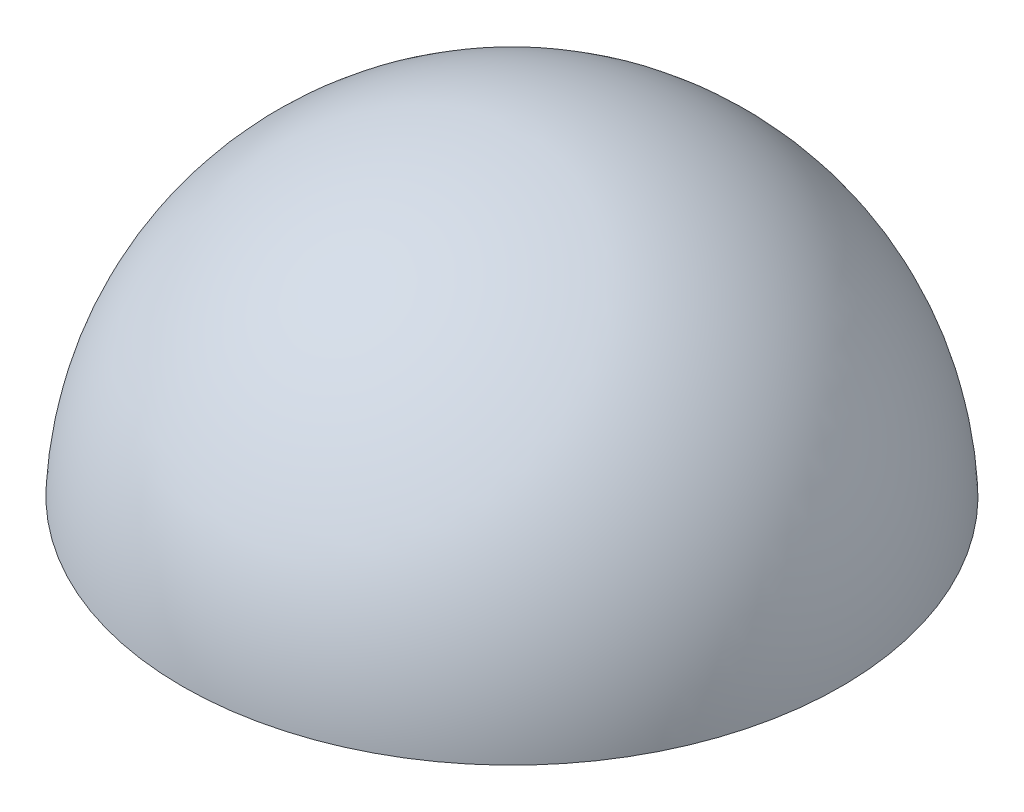
SolidWorks part; units mm, degrees
ref_plane "Front Plane" through (0, 0, 0) normal (0, 0, 1) x (1, 0, 0)
ref_plane "Top Plane" through (0, 0, 0) normal (0, 1, 0) x (1, 0, 0)
ref_plane "Right Plane" through (0, 0, 0) normal (1, 0, 0) x (0, 0, -1)
sketch "Sketch1" plane through (0, 0, 0) normal (0, 1, 0) x (1, 0, 0)
  line L0 (0, -44.45) -> (0, 44.45)
  arc A0 (0, 44.45) -> (0, -44.45) centre (0, 0) ccw
  arc A1 (0, 42.45) -> (0, -42.45) centre (0, 0) ccw
  circle A3 centre (0, 0) radius 44.45 construction
  circle A4 centre (0, 0) radius 42.45 construction
  point P1 (42.45, 0)
  point P6 (42.5077, 12.9959)
  dimension "D1" = 88.9
  dimension "D2" = 2
revolve "Revolve1" add sketch "Sketch1" angle 180 about L0 region at (-43.4561, 0, 0)
sketch "Sketch2" plane through (0, 0, 0) normal (0, 1, 0) x (1, 0, 0)
  circle A0 centre (0, 0) radius 44.45
extrude "Cut-Extrude1" cut sketch "Sketch2" along normal blind 2
sketch "30deg" plane through (0, 0, 0) normal (1, 0, 0) x (0, 0, -1)
  line L0 (0, 0) -> (38.4948, 22.225) construction
  line L1 (0, 0) -> (44.45, 0) construction
  line L7 (0, 0) -> (22.225, 38.4948) construction
  line L8 (0, 0) -> (44.45, 0) construction
  line L10 (0, 0) -> (38.4948, 22.225) construction
  line L25 (0, 0) -> (0, 49000) construction
  dimension "D2" = 3
  dimension "D3" = 30
  dimension "D1" = 44.45
sketch "Sketch4" plane through (0, 0, 0) normal (0, 1, 0) x (1, 0, 0)
  line L0 (0, 0) -> (0, 43.45)
  line L1 (0.5, 44.45) -> (-0.5, 44.45)
  line L2 (-0.5, 43.45) -> (0.5, 43.45)
  line L3 (-0.5, 43.45) -> (-0.5, 44.45)
  line L4 (0.5, 43.45) -> (0.5, 44.45)
  line L5 (0, 0) -> (21.725, 37.6288)
  line L6 (21.292, 37.8788) -> (21.792, 38.7448)
  line L7 (21.292, 37.8788) -> (22.158, 37.3788)
  line L8 (22.158, 37.3788) -> (22.658, 38.2448)
  line L9 (22.658, 38.2448) -> (21.792, 38.7448)
  line L10 (0, 0) -> (37.6288, 21.725)
  line L11 (37.3788, 22.158) -> (38.2448, 22.658)
  line L12 (37.3788, 22.158) -> (37.8788, 21.292)
  line L13 (37.8788, 21.292) -> (38.7448, 21.792)
  line L14 (38.7448, 21.792) -> (38.2448, 22.658)
  line L15 (0, 0) -> (43.45, 0)
  line L16 (43.45, 0.5) -> (44.45, 0.5)
  line L17 (43.45, 0.5) -> (43.45, -0.5)
  line L18 (43.45, -0.5) -> (44.45, -0.5)
  line L19 (44.45, -0.5) -> (44.45, 0.5)
  line L20 (0, 0) -> (37.6288, -21.725)
  line L21 (37.8788, -21.292) -> (38.7448, -21.792)
  line L22 (37.8788, -21.292) -> (37.3788, -22.158)
  line L23 (37.3788, -22.158) -> (38.2448, -22.658)
  line L24 (38.2448, -22.658) -> (38.7448, -21.792)
  line L25 (0, 0) -> (21.725, -37.6288)
  line L26 (22.158, -37.3788) -> (22.658, -38.2448)
  line L27 (22.158, -37.3788) -> (21.292, -37.8788)
  line L28 (21.292, -37.8788) -> (21.792, -38.7448)
  line L29 (21.792, -38.7448) -> (22.658, -38.2448)
  line L30 (0, 0) -> (0, -43.45)
  line L31 (0.5, -43.45) -> (0.5, -44.45)
  line L32 (0.5, -43.45) -> (-0.5, -43.45)
  line L33 (-0.5, -43.45) -> (-0.5, -44.45)
  line L34 (-0.5, -44.45) -> (0.5, -44.45)
  line L35 (0, 0) -> (-21.725, -37.6288)
  line L36 (-21.292, -37.8788) -> (-21.792, -38.7448)
  line L37 (-21.292, -37.8788) -> (-22.158, -37.3788)
  line L38 (-22.158, -37.3788) -> (-22.658, -38.2448)
  line L39 (-22.658, -38.2448) -> (-21.792, -38.7448)
  line L40 (0, 0) -> (-37.6288, -21.725)
  line L41 (-37.3788, -22.158) -> (-38.2448, -22.658)
  line L42 (-37.3788, -22.158) -> (-37.8788, -21.292)
  line L43 (-37.8788, -21.292) -> (-38.7448, -21.792)
  line L44 (-38.7448, -21.792) -> (-38.2448, -22.658)
  line L45 (0, 0) -> (-43.45, 0)
  line L46 (-43.45, -0.5) -> (-44.45, -0.5)
  line L47 (-43.45, -0.5) -> (-43.45, 0.5)
  line L48 (-43.45, 0.5) -> (-44.45, 0.5)
  line L49 (-44.45, 0.5) -> (-44.45, -0.5)
  line L50 (0, 0) -> (-37.6288, 21.725)
  line L51 (-37.8788, 21.292) -> (-38.7448, 21.792)
  line L52 (-37.8788, 21.292) -> (-37.3788, 22.158)
  line L53 (-37.3788, 22.158) -> (-38.2448, 22.658)
  line L54 (-38.2448, 22.658) -> (-38.7448, 21.792)
  line L55 (0, 0) -> (-21.725, 37.6288)
  line L56 (-22.158, 37.3788) -> (-22.658, 38.2448)
  line L57 (-22.158, 37.3788) -> (-21.292, 37.8788)
  line L58 (-21.292, 37.8788) -> (-21.792, 38.7448)
  line L59 (-21.792, 38.7448) -> (-22.658, 38.2448)
  line L60 (0, 0) -> (0, 43.45) construction
  line L61 (0, 0) -> (21.725, 37.6288) construction
  circle A0 centre (0, 0) radius 44.45 construction
  point P7 (0, 44.45)
  point P10 (0, 43.45)
  dimension "D1" = 88.9
  dimension "D2" = 1
  dimension "D3" = 1
  dimension "D5" = 30
  dimension "D4" = 12
ref_plane "Plane1" through (0, 44.45, 0) normal (0, 1, 0) x (1, 0, 0)
sketch "Sketch5" plane through (0, 44.45, 0) normal (0, 1, 0) x (1, 0, 0)
  circle A0 centre (0, 0) radius 0.5
  dimension "D1" = 1
sketch "Sketch6" plane through (0, 0, 0) normal (0, 0, 1) x (1, 0, 0)
  line L0 (44.45, 0) -> (-44.45, 0) construction
  line L1 (-43.45, 0) -> (-44.45, 0) construction
  arc A0 (-44.45, 0) -> (0, 44.45) centre (0, 0) cw
ref_axis "Axis1" through (0, 117.8347, 0) along (0, -1, 0)
sketch "Sketch7" plane through (0, 44.45, 0) normal (0, 1, 0) x (1, 0, 0)
  line L0 (0, 0) -> (0, 88.8986) construction
  line L4 (-0.5, 38.9916) -> (-0.5, 88.8986)
  line L5 (0.5, 38.9916) -> (0.5, 88.8986)
  line L7 (-0.5, 22.7195) -> (-0.5, 37.9915)
  line L9 (0.5, 22.7195) -> (0.5, 37.9915)
  line L10 (0, 0) -> (44.4493, 76.9884) construction
  line L11 (19.0628, 34.0177) -> (44.0163, 77.2384)
  line L12 (19.9288, 33.5177) -> (44.8823, 76.7384)
  line L13 (10.9267, 19.9257) -> (18.5628, 33.1516)
  line L14 (11.7928, 19.4257) -> (19.4288, 32.6516)
  line L17 (0, 0) -> (76.9884, 44.4493) construction
  line L18 (33.5177, 19.9288) -> (76.7384, 44.8823)
  line L19 (34.0177, 19.0628) -> (77.2384, 44.0163)
  line L20 (19.4257, 11.7928) -> (32.6516, 19.4288)
  line L21 (19.9257, 10.9267) -> (33.1516, 18.5628)
  line L24 (0, 0) -> (88.8986, 0) construction
  line L25 (38.9916, 0.5) -> (88.8986, 0.5)
  line L26 (38.9916, -0.5) -> (88.8986, -0.5)
  line L27 (22.7195, 0.5) -> (37.9915, 0.5)
  line L28 (22.7195, -0.5) -> (37.9915, -0.5)
  line L31 (0, 0) -> (76.9884, -44.4493) construction
  line L32 (34.0177, -19.0628) -> (77.2384, -44.0163)
  line L33 (33.5177, -19.9288) -> (76.7384, -44.8823)
  line L34 (19.9257, -10.9267) -> (33.1516, -18.5628)
  line L35 (19.4257, -11.7928) -> (32.6516, -19.4288)
  line L38 (0, 0) -> (44.4493, -76.9884) construction
  line L39 (19.9288, -33.5177) -> (44.8823, -76.7384)
  line L40 (19.0628, -34.0177) -> (44.0163, -77.2384)
  line L41 (11.7928, -19.4257) -> (19.4288, -32.6516)
  line L42 (10.9267, -19.9257) -> (18.5628, -33.1516)
  line L45 (0, 0) -> (0, -88.8986) construction
  line L46 (0.5, -38.9916) -> (0.5, -88.8986)
  line L47 (-0.5, -38.9916) -> (-0.5, -88.8986)
  line L48 (0.5, -22.7195) -> (0.5, -37.9915)
  line L49 (-0.5, -22.7195) -> (-0.5, -37.9915)
  line L52 (0, 0) -> (-44.4493, -76.9884) construction
  line L53 (-19.0628, -34.0177) -> (-44.0163, -77.2384)
  line L54 (-19.9288, -33.5177) -> (-44.8823, -76.7384)
  line L55 (-10.9267, -19.9257) -> (-18.5628, -33.1516)
  line L56 (-11.7928, -19.4257) -> (-19.4288, -32.6516)
  line L59 (0, 0) -> (-76.9884, -44.4493) construction
  line L60 (-33.5177, -19.9288) -> (-76.7384, -44.8823)
  line L61 (-34.0177, -19.0628) -> (-77.2384, -44.0163)
  line L62 (-19.4257, -11.7928) -> (-32.6516, -19.4288)
  line L63 (-19.9257, -10.9267) -> (-33.1516, -18.5628)
  line L66 (0, 0) -> (-88.8986, 0) construction
  line L67 (-38.9916, -0.5) -> (-88.8986, -0.5)
  line L68 (-38.9916, 0.5) -> (-88.8986, 0.5)
  line L69 (-22.7195, -0.5) -> (-37.9915, -0.5)
  line L70 (-22.7195, 0.5) -> (-37.9915, 0.5)
  line L73 (0, 0) -> (-76.9884, 44.4493) construction
  line L74 (-34.0177, 19.0628) -> (-77.2384, 44.0163)
  line L75 (-33.5177, 19.9288) -> (-76.7384, 44.8823)
  line L76 (-19.9257, 10.9267) -> (-33.1516, 18.5628)
  line L77 (-19.4257, 11.7928) -> (-32.6516, 19.4288)
  line L80 (0, 0) -> (-44.4493, 76.9884) construction
  line L81 (-19.9288, 33.5177) -> (-44.8823, 76.7384)
  line L82 (-19.0628, 34.0177) -> (-44.0163, 77.2384)
  line L83 (-11.7928, 19.4257) -> (-19.4288, 32.6516)
  line L84 (-10.9267, 19.9257) -> (-18.5628, 33.1516)
  line L87 (0, 0) -> (0.5, 0) construction
  line L89 (-0.5, 1.866) -> (-0.5, 21.7192)
  line L90 (-0.5, 1.866) -> (-10.4266, 19.0594)
  line L91 (0.5, 1.866) -> (10.4266, 19.0594)
  line L92 (0.5, 1.866) -> (0.5, 21.7192)
  line L93 (1.366, 1.366) -> (18.5594, 11.2926)
  line L94 (1.366, 1.366) -> (11.2926, 18.5594)
  line L95 (1.866, 0.5) -> (21.7192, 0.5)
  line L96 (1.866, 0.5) -> (19.0594, 10.4266)
  line L97 (1.866, -0.5) -> (19.0594, -10.4266)
  line L98 (1.866, -0.5) -> (21.7192, -0.5)
  line L99 (1.366, -1.366) -> (11.2926, -18.5594)
  line L100 (1.366, -1.366) -> (18.5594, -11.2926)
  line L101 (0.5, -1.866) -> (0.5, -21.7192)
  line L102 (0.5, -1.866) -> (10.4266, -19.0594)
  line L103 (-0.5, -1.866) -> (-10.4266, -19.0594)
  line L104 (-0.5, -1.866) -> (-0.5, -21.7192)
  line L105 (-1.366, -1.366) -> (-11.2926, -18.5594)
  line L106 (-1.366, -1.366) -> (-18.5594, -11.2926)
  line L107 (-1.866, -0.5) -> (-21.7192, -0.5)
  line L108 (-1.866, -0.5) -> (-19.0594, -10.4266)
  line L109 (-1.866, 0.5) -> (-19.0594, 10.4266)
  line L110 (-1.866, 0.5) -> (-21.7192, 0.5)
  line L111 (-1.366, 1.366) -> (-11.2926, 18.5594)
  line L112 (-1.366, 1.366) -> (-18.5594, 11.2926)
  circle A0 centre (0, 0) radius 22.225 construction
  circle A1 centre (0, 0) radius 38.4948 construction
  arc A2 (-0.5, 38.9916) -> (-19.0628, 34.0177) centre (0, 0) ccw
  arc A3 (-0.5, 22.7195) -> (-10.9267, 19.9257) centre (0, 0) ccw
  arc A4 (-0.5, 37.9915) -> (-18.5628, 33.1516) centre (0, 0) ccw
  arc A5 (-0.5, 21.7192) -> (-10.4266, 19.0594) centre (0, 0) ccw
  arc A6 (0.5, 88.8986) -> (-0.5, 88.8986) centre (0, 0) ccw
  circle A9 centre (0, 0) radius 88.9 construction
  circle A10 centre (0, 0) radius 38.9948 construction
  circle A11 centre (0, 0) radius 37.9948 construction
  circle A13 centre (0, 0) radius 21.725 construction
  circle A14 centre (0, 0) radius 22.725 construction
  arc A15 (44.8823, 76.7384) -> (44.0163, 77.2384) centre (0, 0) ccw
  arc A16 (77.2384, 44.0163) -> (76.7384, 44.8823) centre (0, 0) ccw
  arc A17 (88.8986, -0.5) -> (88.8986, 0.5) centre (0, 0) ccw
  arc A18 (76.7384, -44.8823) -> (77.2384, -44.0163) centre (0, 0) ccw
  arc A19 (44.0163, -77.2384) -> (44.8823, -76.7384) centre (0, 0) ccw
  arc A20 (-0.5, -88.8986) -> (0.5, -88.8986) centre (0, 0) ccw
  arc A21 (-44.8823, -76.7384) -> (-44.0163, -77.2384) centre (0, 0) ccw
  arc A22 (-77.2384, -44.0163) -> (-76.7384, -44.8823) centre (0, 0) ccw
  arc A23 (-88.8986, 0.5) -> (-88.8986, -0.5) centre (0, 0) ccw
  arc A24 (-76.7384, 44.8823) -> (-77.2384, 44.0163) centre (0, 0) ccw
  arc A25 (-44.0163, 77.2384) -> (-44.8823, 76.7384) centre (0, 0) ccw
  arc A26 (-34.0177, 19.0628) -> (-38.9916, 0.5) centre (0, 0) ccw
  arc A27 (-33.1516, 18.5628) -> (-37.9915, 0.5) centre (0, 0) ccw
  arc A28 (-19.9288, 33.5177) -> (-33.5177, 19.9288) centre (0, 0) ccw
  arc A29 (-19.4288, 32.6516) -> (-32.6516, 19.4288) centre (0, 0) ccw
  arc A30 (19.0628, 34.0177) -> (0.5, 38.9916) centre (0, 0) ccw
  arc A31 (18.5628, 33.1516) -> (0.5, 37.9915) centre (0, 0) ccw
  arc A32 (32.6516, 19.4288) -> (19.4288, 32.6516) centre (0, 0) ccw
  arc A33 (33.5177, 19.9288) -> (19.9288, 33.5177) centre (0, 0) ccw
  arc A34 (37.9915, 0.5) -> (33.1516, 18.5628) centre (0, 0) ccw
  arc A35 (38.9916, 0.5) -> (34.0177, 19.0628) centre (0, 0) ccw
  arc A36 (33.1516, -18.5628) -> (37.9915, -0.5) centre (0, 0) ccw
  arc A37 (34.0177, -19.0628) -> (38.9916, -0.5) centre (0, 0) ccw
  arc A38 (19.4288, -32.6516) -> (32.6516, -19.4288) centre (0, 0) ccw
  arc A39 (19.9288, -33.5177) -> (33.5177, -19.9288) centre (0, 0) ccw
  arc A40 (0.5, -37.9915) -> (18.5628, -33.1516) centre (0, 0) ccw
  arc A41 (0.5, -38.9916) -> (19.0628, -34.0177) centre (0, 0) ccw
  arc A42 (-18.5628, -33.1516) -> (-0.5, -37.9915) centre (0, 0) ccw
  arc A43 (-19.0628, -34.0177) -> (-0.5, -38.9916) centre (0, 0) ccw
  arc A44 (-33.5177, -19.9288) -> (-19.9288, -33.5177) centre (0, 0) ccw
  arc A45 (-32.6516, -19.4288) -> (-19.4288, -32.6516) centre (0, 0) ccw
  arc A46 (-38.9916, -0.5) -> (-34.0177, -19.0628) centre (0, 0) ccw
  arc A47 (-37.9915, -0.5) -> (-33.1516, -18.5628) centre (0, 0) ccw
  arc A48 (-11.7928, 19.4257) -> (-19.4257, 11.7928) centre (0, 0) ccw
  arc A49 (-11.2926, 18.5594) -> (-18.5594, 11.2926) centre (0, 0) ccw
  arc A50 (-19.9257, 10.9267) -> (-22.7195, 0.5) centre (0, 0) ccw
  arc A51 (-19.0594, 10.4266) -> (-21.7192, 0.5) centre (0, 0) ccw
  arc A52 (-21.7192, -0.5) -> (-19.0594, -10.4266) centre (0, 0) ccw
  arc A53 (-22.7195, -0.5) -> (-19.9257, -10.9267) centre (0, 0) ccw
  arc A54 (10.4266, 19.0594) -> (0.5, 21.7192) centre (0, 0) ccw
  arc A55 (10.9267, 19.9257) -> (0.5, 22.7195) centre (0, 0) ccw
  arc A56 (18.5594, 11.2926) -> (11.2926, 18.5594) centre (0, 0) ccw
  arc A57 (19.4257, 11.7928) -> (11.7928, 19.4257) centre (0, 0) ccw
  arc A58 (21.7192, 0.5) -> (19.0594, 10.4266) centre (0, 0) ccw
  arc A59 (22.7195, 0.5) -> (19.9257, 10.9267) centre (0, 0) ccw
  arc A60 (19.9257, -10.9267) -> (22.7195, -0.5) centre (0, 0) ccw
  arc A61 (19.0594, -10.4266) -> (21.7192, -0.5) centre (0, 0) ccw
  arc A62 (11.2926, -18.5594) -> (18.5594, -11.2926) centre (0, 0) ccw
  arc A63 (11.7928, -19.4257) -> (19.4257, -11.7928) centre (0, 0) ccw
  arc A64 (0.5, -22.7195) -> (10.9267, -19.9257) centre (0, 0) ccw
  arc A65 (0.5, -21.7192) -> (10.4266, -19.0594) centre (0, 0) ccw
  arc A66 (-10.4266, -19.0594) -> (-0.5, -21.7192) centre (0, 0) ccw
  arc A67 (-10.9267, -19.9257) -> (-0.5, -22.7195) centre (0, 0) ccw
  arc A68 (-19.4257, -11.7928) -> (-11.7928, -19.4257) centre (0, 0) ccw
  arc A69 (-18.5594, -11.2926) -> (-11.2926, -18.5594) centre (0, 0) ccw
  point P11 (21.725, 0)
  point P13 (22.725, 0)
  point P17 (0.5, 0)
  point P19 (-0.5, 0)
  point P27 (38.9948, 0)
  point P30 (37.9948, 0)
  point P114 (-1.366, 1.366)
  dimension "D5" = 177.8
  dimension "D1" = 0.5
  dimension "D2" = 0.5
  dimension "D6" = 12
sketch "Sketch9" plane through (0, 44.45, 0) normal (0, 1, 0) x (1, 0, 0)
  line L0 (0, 0) -> (0, -88.9)
  circle A0 centre (0, 0) radius 22.225
  circle A1 centre (0, 0) radius 38.4948
  circle A2 centre (0, 0) radius 88.9
  circle A3 centre (0, 0) radius 38.4948 construction
  circle A4 centre (0, 0) radius 22.225 construction
  dimension "D1" = 177.8
sketch "Sketch10" plane through (0, 44.45, 0) normal (0, 1, 0) x (1, 0, 0)
  line L0 (88.9, 0) -> (-88.9, 0) construction
  line L1 (0, 88.9) -> (0, -88.9) construction
  line L2 (-29.64, 88.9) -> (-29.64, -88.9) construction
  line L3 (-59.28, 88.9) -> (-59.28, -88.9) construction
  line L4 (-88.92, 88.9) -> (-88.92, -88.9) construction
  line L5 (29.64, 88.9) -> (29.64, -88.9) construction
  line L6 (59.28, 88.9) -> (59.28, -88.9) construction
  line L7 (88.92, 88.9) -> (88.92, -88.9) construction
  line L8 (-89.42, 88.9) -> (-89.42, -88.9)
  line L9 (-59.78, 88.9) -> (-59.78, 0.5)
  line L10 (-30.14, 88.9) -> (-30.14, 0.5)
  line L11 (-0.5, 88.9) -> (-0.5, 0.5)
  line L12 (29.14, 88.9) -> (29.14, 0.5)
  line L13 (58.78, 88.9) -> (58.78, 0.5)
  line L14 (88.42, 88.9) -> (88.42, 0.5)
  line L15 (-88.42, 88.9) -> (-88.42, 0.5)
  line L16 (-58.78, 88.9) -> (-58.78, 0.5)
  line L17 (-29.14, 88.9) -> (-29.14, 0.5)
  line L18 (0.5, 88.9) -> (0.5, 0.5)
  line L19 (30.14, 88.9) -> (30.14, 0.5)
  line L20 (59.78, 88.9) -> (59.78, 0.5)
  line L21 (89.42, 88.9) -> (89.42, -88.9)
  line L22 (88.42, 0.5) -> (59.78, 0.5)
  line L23 (88.42, -0.5) -> (59.78, -0.5)
  line L24 (-88.42, -0.5) -> (-88.42, -88.9)
  line L25 (88.9, 0.5) -> (-88.9, 0.5) construction
  line L26 (88.9, -0.5) -> (-88.9, -0.5) construction
  line L27 (-59.78, 0.5) -> (-88.42, 0.5)
  line L28 (-88.42, 88.9) -> (-88.42, -88.9) construction
  line L29 (-59.78, -0.5) -> (-88.42, -0.5)
  line L30 (-59.78, -0.5) -> (-59.78, -88.9)
  line L31 (-58.78, -0.5) -> (-58.78, -88.9)
  line L32 (-59.78, 88.9) -> (-59.78, -88.9) construction
  line L33 (-30.14, -0.5) -> (-30.14, -88.9)
  line L34 (-58.78, 88.9) -> (-58.78, -88.9) construction
  line L35 (-30.14, 88.9) -> (-30.14, -88.9) construction
  line L36 (-29.14, -0.5) -> (-29.14, -88.9)
  line L37 (-29.14, 88.9) -> (-29.14, -88.9) construction
  line L38 (-0.5, -0.5) -> (-0.5, -88.9)
  line L39 (-0.5, 88.9) -> (-0.5, -88.9) construction
  line L40 (0.5, -0.5) -> (0.5, -88.9)
  line L41 (0.5, 88.9) -> (0.5, -88.9) construction
  line L42 (29.14, -0.5) -> (29.14, -88.9)
  line L43 (29.14, 88.9) -> (29.14, -88.9) construction
  line L44 (30.14, -0.5) -> (30.14, -88.9)
  line L45 (30.14, 88.9) -> (30.14, -88.9) construction
  line L46 (58.78, -0.5) -> (58.78, -88.9)
  line L47 (58.78, 88.9) -> (58.78, -88.9) construction
  line L48 (59.78, -0.5) -> (59.78, -88.9)
  line L49 (59.78, 88.9) -> (59.78, -88.9) construction
  line L50 (88.42, -0.5) -> (88.42, -88.9)
  line L51 (88.42, 88.9) -> (88.42, -88.9) construction
  line L52 (58.78, 0.5) -> (30.14, 0.5)
  line L53 (58.78, -0.5) -> (30.14, -0.5)
  line L54 (-30.14, 0.5) -> (-58.78, 0.5)
  line L55 (-30.14, -0.5) -> (-58.78, -0.5)
  line L56 (-0.5, 0.5) -> (-29.14, 0.5)
  line L57 (-0.5, -0.5) -> (-29.14, -0.5)
  line L58 (29.14, 0.5) -> (0.5, 0.5)
  line L59 (29.14, -0.5) -> (0.5, -0.5)
  arc A0 (-89.42, 88.9) -> (-88.42, 88.9) centre (-88.92, 88.9) cw
  arc A1 (-89.42, -88.9) -> (-88.42, -88.9) centre (-88.92, -88.9) ccw
  arc A2 (-59.78, 88.9) -> (-58.78, 88.9) centre (-59.28, 88.9) cw
  arc A3 (-59.78, -88.9) -> (-58.78, -88.9) centre (-59.28, -88.9) ccw
  arc A4 (-30.14, 88.9) -> (-29.14, 88.9) centre (-29.64, 88.9) cw
  arc A5 (-30.14, -88.9) -> (-29.14, -88.9) centre (-29.64, -88.9) ccw
  arc A6 (-0.5, 88.9) -> (0.5, 88.9) centre (0, 88.9) cw
  arc A7 (-0.5, -88.9) -> (0.5, -88.9) centre (0, -88.9) ccw
  arc A8 (29.14, 88.9) -> (30.14, 88.9) centre (29.64, 88.9) cw
  arc A9 (29.14, -88.9) -> (30.14, -88.9) centre (29.64, -88.9) ccw
  arc A10 (58.78, 88.9) -> (59.78, 88.9) centre (59.28, 88.9) cw
  arc A11 (58.78, -88.9) -> (59.78, -88.9) centre (59.28, -88.9) ccw
  arc A12 (88.42, 88.9) -> (89.42, 88.9) centre (88.92, 88.9) cw
  arc A13 (88.42, -88.9) -> (89.42, -88.9) centre (88.92, -88.9) ccw
  arc A15 (-88.9, 0.5) -> (-88.92, 0.4996) centre (-88.9, 0) ccw
  arc A16 (-88.92, -0.4996) -> (-88.9, -0.5) centre (-88.9, 0) ccw
  point P4 (0, 0)
  point P8 (0, 0)
  dimension "D1" = 177.8
  dimension "D3" = 0.5
  dimension "D4" = 0.5
  dimension "D5" = 0.5
  dimension "D6" = 0.5
  dimension "D2" = 4
sketch "Sketch13" plane through (0, 44.45, 0) normal (0, 1, 0) x (1, 0, 0)
  line L0 (0, -11.5265) -> (0, 11.5265) construction
  line L1 (-11.5265, 0) -> (11.5265, 0) construction
  line L2 (-11.5265, -0.5) -> (-0.5, -0.5)
  line L3 (-18.1069, 3.2902) -> (-11.5265, 3.2902) construction
  line L4 (-18.1069, 3.2902) -> (-18.1069, -3.2902) construction
  line L5 (-18.1069, -3.2902) -> (-11.5265, -3.2902) construction
  line L6 (-11.5265, 3.2902) -> (-11.5265, -3.2902) construction
  line L7 (-3.2902, 18.1069) -> (3.2902, 18.1069) construction
  line L8 (-3.2902, 18.1069) -> (-3.2902, 11.5265) construction
  line L9 (-3.2902, 11.5265) -> (3.2902, 11.5265) construction
  line L10 (3.2902, 18.1069) -> (3.2902, 11.5265) construction
  line L11 (0.5, -11.5265) -> (0.5, -0.5)
  line L12 (-11.5265, 0.5) -> (-0.5, 0.5)
  line L13 (-0.5, -11.5265) -> (-0.5, -0.5)
  line L14 (-0.5, 0.5) -> (-0.5, 11.5265)
  line L15 (0.5, 0.5) -> (0.5, 11.5265)
  line L16 (-0.5, -11.5265) -> (-0.5, 11.5265) construction
  line L17 (0.5, 0.5) -> (11.5265, 0.5)
  line L18 (0.5, -11.5265) -> (0.5, 11.5265) construction
  line L19 (0.5, -0.5) -> (11.5265, -0.5)
  line L20 (-11.5265, 0.5) -> (11.5265, 0.5) construction
  line L21 (-11.5265, 0.5) -> (-11.5265, -0.5)
  line L22 (-11.5265, -0.5) -> (11.5265, -0.5) construction
  line L23 (11.5265, 0.5) -> (11.5265, -0.5)
  line L24 (-0.5, -11.5265) -> (0.5, -11.5265)
  line L25 (-0.5, 11.5265) -> (0.5, 11.5265)
  line L26 (18.1035, -0.5) -> (29.13, -0.5)
  line L27 (30.13, -11.5265) -> (30.13, -0.5)
  line L28 (18.1035, 0.5) -> (29.13, 0.5)
  line L29 (29.13, -11.5265) -> (29.13, -0.5)
  line L30 (29.13, 0.5) -> (29.13, 11.5265)
  line L31 (30.13, 0.5) -> (30.13, 11.5265)
  line L32 (30.13, 0.5) -> (41.1565, 0.5)
  line L33 (30.13, -0.5) -> (41.1565, -0.5)
  line L34 (18.1035, 0.5) -> (18.1035, -0.5)
  line L35 (41.1565, 0.5) -> (41.1565, -0.5)
  line L36 (29.13, -11.5265) -> (30.13, -11.5265)
  line L37 (29.13, 11.5265) -> (30.13, 11.5265)
  line L38 (29.63, -11.5265) -> (29.63, 11.5265) construction
  line L39 (18.1035, 0) -> (41.1565, 0) construction
  line L40 (11.5231, 3.2902) -> (18.1035, 3.2902) construction
  line L41 (11.5231, 3.2902) -> (11.5231, -3.2902) construction
  line L42 (11.5231, -3.2902) -> (18.1035, -3.2902) construction
  line L43 (18.1035, 3.2902) -> (18.1035, -3.2902) construction
  line L44 (26.3398, 18.1069) -> (32.9202, 18.1069) construction
  line L45 (26.3398, 18.1069) -> (26.3398, 11.5265) construction
  line L46 (26.3398, 11.5265) -> (32.9202, 11.5265) construction
  line L47 (32.9202, 18.1069) -> (32.9202, 11.5265) construction
  line L48 (47.7335, -0.5) -> (58.76, -0.5)
  line L49 (59.76, -11.5265) -> (59.76, -0.5)
  line L50 (47.7335, 0.5) -> (58.76, 0.5)
  line L51 (58.76, -11.5265) -> (58.76, -0.5)
  line L52 (58.76, 0.5) -> (58.76, 11.5265)
  line L53 (59.76, 0.5) -> (59.76, 11.5265)
  line L54 (59.76, 0.5) -> (70.7865, 0.5)
  line L55 (59.76, -0.5) -> (70.7865, -0.5)
  line L56 (47.7335, 0.5) -> (47.7335, -0.5)
  line L57 (70.7865, 0.5) -> (70.7865, -0.5)
  line L58 (58.76, -11.5265) -> (59.76, -11.5265)
  line L59 (58.76, 11.5265) -> (59.76, 11.5265)
  line L60 (59.26, -11.5265) -> (59.26, 11.5265) construction
  line L61 (47.7335, 0) -> (70.7865, 0) construction
  line L62 (41.1531, 3.2902) -> (47.7335, 3.2902) construction
  line L63 (41.1531, 3.2902) -> (41.1531, -3.2902) construction
  line L64 (41.1531, -3.2902) -> (47.7335, -3.2902) construction
  line L65 (47.7335, 3.2902) -> (47.7335, -3.2902) construction
  line L66 (55.9698, 18.1069) -> (62.5502, 18.1069) construction
  line L67 (55.9698, 18.1069) -> (55.9698, 11.5265) construction
  line L68 (55.9698, 11.5265) -> (62.5502, 11.5265) construction
  line L69 (62.5502, 18.1069) -> (62.5502, 11.5265) construction
  line L70 (-11.5265, 29.13) -> (-0.5, 29.13)
  line L71 (0.5, 18.1035) -> (0.5, 29.13)
  line L72 (-11.5265, 30.13) -> (-0.5, 30.13)
  line L73 (-0.5, 18.1035) -> (-0.5, 29.13)
  line L74 (-0.5, 30.13) -> (-0.5, 41.1565)
  line L75 (0.5, 30.13) -> (0.5, 41.1565)
  line L76 (0.5, 30.13) -> (11.5265, 30.13)
  line L77 (0.5, 29.13) -> (11.5265, 29.13)
  line L78 (-11.5265, 30.13) -> (-11.5265, 29.13)
  line L79 (11.5265, 30.13) -> (11.5265, 29.13)
  line L80 (-0.5, 18.1035) -> (0.5, 18.1035)
  line L81 (-0.5, 41.1565) -> (0.5, 41.1565)
  line L82 (18.1035, 29.13) -> (29.13, 29.13)
  line L83 (30.13, 18.1035) -> (30.13, 29.13)
  line L84 (18.1035, 30.13) -> (29.13, 30.13)
  line L85 (29.13, 18.1035) -> (29.13, 29.13)
  line L86 (29.13, 30.13) -> (29.13, 41.1565)
  line L87 (30.13, 30.13) -> (30.13, 41.1565)
  line L88 (30.13, 30.13) -> (41.1565, 30.13)
  line L89 (30.13, 29.13) -> (41.1565, 29.13)
  line L90 (18.1035, 30.13) -> (18.1035, 29.13)
  line L91 (41.1565, 30.13) -> (41.1565, 29.13)
  line L92 (29.13, 18.1035) -> (30.13, 18.1035)
  line L93 (29.13, 41.1565) -> (30.13, 41.1565)
  line L94 (47.7335, 29.13) -> (58.76, 29.13)
  line L95 (59.76, 18.1035) -> (59.76, 29.13)
  line L96 (47.7335, 30.13) -> (58.76, 30.13)
  line L97 (58.76, 18.1035) -> (58.76, 29.13)
  line L98 (58.76, 30.13) -> (58.76, 41.1565)
  line L99 (59.76, 30.13) -> (59.76, 41.1565)
  line L100 (59.76, 30.13) -> (70.7865, 30.13)
  line L101 (59.76, 29.13) -> (70.7865, 29.13)
  line L102 (47.7335, 30.13) -> (47.7335, 29.13)
  line L103 (70.7865, 30.13) -> (70.7865, 29.13)
  line L104 (58.76, 18.1035) -> (59.76, 18.1035)
  line L105 (58.76, 41.1565) -> (59.76, 41.1565)
  line L106 (0, 18.1035) -> (0, 41.1565) construction
  line L107 (-11.5265, 29.63) -> (11.5265, 29.63) construction
  line L108 (-18.1069, 32.9202) -> (-11.5265, 32.9202) construction
  line L109 (-18.1069, 32.9202) -> (-18.1069, 26.3398) construction
  line L110 (-18.1069, 26.3398) -> (-11.5265, 26.3398) construction
  line L111 (-11.5265, 32.9202) -> (-11.5265, 26.3398) construction
  line L112 (-3.2902, 47.7369) -> (3.2902, 47.7369) construction
  line L113 (-3.2902, 47.7369) -> (-3.2902, 41.1565) construction
  line L114 (-3.2902, 41.1565) -> (3.2902, 41.1565) construction
  line L115 (3.2902, 47.7369) -> (3.2902, 41.1565) construction
  line L116 (29.63, 18.1035) -> (29.63, 41.1565) construction
  line L117 (18.1035, 29.63) -> (41.1565, 29.63) construction
  line L118 (11.5231, 32.9202) -> (18.1035, 32.9202) construction
  line L119 (11.5231, 32.9202) -> (11.5231, 26.3398) construction
  line L120 (11.5231, 26.3398) -> (18.1035, 26.3398) construction
  line L121 (18.1035, 32.9202) -> (18.1035, 26.3398) construction
  line L122 (26.3398, 47.7369) -> (32.9202, 47.7369) construction
  line L123 (26.3398, 47.7369) -> (26.3398, 41.1565) construction
  line L124 (26.3398, 41.1565) -> (32.9202, 41.1565) construction
  line L125 (32.9202, 47.7369) -> (32.9202, 41.1565) construction
  line L126 (59.26, 18.1035) -> (59.26, 41.1565) construction
  line L127 (47.7335, 29.63) -> (70.7865, 29.63) construction
  line L128 (41.1531, 32.9202) -> (47.7335, 32.9202) construction
  line L129 (41.1531, 32.9202) -> (41.1531, 26.3398) construction
  line L130 (41.1531, 26.3398) -> (47.7335, 26.3398) construction
  line L131 (47.7335, 32.9202) -> (47.7335, 26.3398) construction
  line L132 (55.9698, 47.7369) -> (62.5502, 47.7369) construction
  line L133 (55.9698, 47.7369) -> (55.9698, 41.1565) construction
  line L134 (55.9698, 41.1565) -> (62.5502, 41.1565) construction
  line L135 (62.5502, 47.7369) -> (62.5502, 41.1565) construction
  line L136 (-11.5265, 58.76) -> (-0.5, 58.76)
  line L137 (0.5, 47.7335) -> (0.5, 58.76)
  line L138 (-11.5265, 59.76) -> (-0.5, 59.76)
  line L139 (-0.5, 47.7335) -> (-0.5, 58.76)
  line L140 (-0.5, 59.76) -> (-0.5, 70.7865)
  line L141 (0.5, 59.76) -> (0.5, 70.7865)
  line L142 (0.5, 59.76) -> (11.5265, 59.76)
  line L143 (0.5, 58.76) -> (11.5265, 58.76)
  line L144 (-11.5265, 59.76) -> (-11.5265, 58.76)
  line L145 (11.5265, 59.76) -> (11.5265, 58.76)
  line L146 (-0.5, 47.7335) -> (0.5, 47.7335)
  line L147 (-0.5, 70.7865) -> (0.5, 70.7865)
  line L148 (18.1035, 58.76) -> (29.13, 58.76)
  line L149 (30.13, 47.7335) -> (30.13, 58.76)
  line L150 (18.1035, 59.76) -> (29.13, 59.76)
  line L151 (29.13, 47.7335) -> (29.13, 58.76)
  line L152 (29.13, 59.76) -> (29.13, 70.7865)
  line L153 (30.13, 59.76) -> (30.13, 70.7865)
  line L154 (30.13, 59.76) -> (41.1565, 59.76)
  line L155 (30.13, 58.76) -> (41.1565, 58.76)
  line L156 (18.1035, 59.76) -> (18.1035, 58.76)
  line L157 (41.1565, 59.76) -> (41.1565, 58.76)
  line L158 (29.13, 47.7335) -> (30.13, 47.7335)
  line L159 (29.13, 70.7865) -> (30.13, 70.7865)
  line L160 (47.7335, 58.76) -> (58.76, 58.76)
  line L161 (59.76, 47.7335) -> (59.76, 58.76)
  line L162 (47.7335, 59.76) -> (58.76, 59.76)
  line L163 (58.76, 47.7335) -> (58.76, 58.76)
  line L164 (58.76, 59.76) -> (58.76, 70.7865)
  line L165 (59.76, 59.76) -> (59.76, 70.7865)
  line L166 (59.76, 59.76) -> (70.7865, 59.76)
  line L167 (59.76, 58.76) -> (70.7865, 58.76)
  line L168 (47.7335, 59.76) -> (47.7335, 58.76)
  line L169 (70.7865, 59.76) -> (70.7865, 58.76)
  line L170 (58.76, 47.7335) -> (59.76, 47.7335)
  line L171 (58.76, 70.7865) -> (59.76, 70.7865)
  line L172 (0, 47.7335) -> (0, 70.7865) construction
  line L173 (-11.5265, 59.26) -> (11.5265, 59.26) construction
  line L174 (-18.1069, 62.5502) -> (-11.5265, 62.5502) construction
  line L175 (-18.1069, 62.5502) -> (-18.1069, 55.9698) construction
  line L176 (-18.1069, 55.9698) -> (-11.5265, 55.9698) construction
  line L177 (-11.5265, 62.5502) -> (-11.5265, 55.9698) construction
  line L178 (-3.2902, 77.3669) -> (3.2902, 77.3669) construction
  line L179 (-3.2902, 77.3669) -> (-3.2902, 70.7865) construction
  line L180 (-3.2902, 70.7865) -> (3.2902, 70.7865) construction
  line L181 (3.2902, 77.3669) -> (3.2902, 70.7865) construction
  line L182 (29.63, 47.7335) -> (29.63, 70.7865) construction
  line L183 (18.1035, 59.26) -> (41.1565, 59.26) construction
  line L184 (11.5231, 62.5502) -> (18.1035, 62.5502) construction
  line L185 (11.5231, 62.5502) -> (11.5231, 55.9698) construction
  line L186 (11.5231, 55.9698) -> (18.1035, 55.9698) construction
  line L187 (18.1035, 62.5502) -> (18.1035, 55.9698) construction
  line L188 (26.3398, 77.3669) -> (32.9202, 77.3669) construction
  line L189 (26.3398, 77.3669) -> (26.3398, 70.7865) construction
  line L190 (26.3398, 70.7865) -> (32.9202, 70.7865) construction
  line L191 (32.9202, 77.3669) -> (32.9202, 70.7865) construction
  line L192 (59.26, 47.7335) -> (59.26, 70.7865) construction
  line L193 (47.7335, 59.26) -> (70.7865, 59.26) construction
  line L194 (41.1531, 62.5502) -> (47.7335, 62.5502) construction
  line L195 (41.1531, 62.5502) -> (41.1531, 55.9698) construction
  line L196 (41.1531, 55.9698) -> (47.7335, 55.9698) construction
  line L197 (47.7335, 62.5502) -> (47.7335, 55.9698) construction
  line L198 (55.9698, 77.3669) -> (62.5502, 77.3669) construction
  line L199 (55.9698, 77.3669) -> (55.9698, 70.7865) construction
  line L200 (55.9698, 70.7865) -> (62.5502, 70.7865) construction
  line L201 (62.5502, 77.3669) -> (62.5502, 70.7865) construction
  circle A0 centre (0, 0) radius 88.9 construction
  point P4 (0, 0)
  point P8 (0, 0)
  point P12 (-11.5265, 0)
  point P35 (29.63, 0)
  point P38 (29.63, 0)
  point P61 (59.26, 0)
  point P64 (59.26, 0)
  point P86 (0, 29.63)
  point P89 (0, 29.63)
  point P112 (29.63, 29.63)
  point P115 (29.63, 29.63)
  point P138 (59.26, 29.63)
  point P141 (59.26, 29.63)
  point P164 (0, 59.26)
  point P167 (0, 59.26)
  point P190 (29.63, 59.26)
  point P193 (29.63, 59.26)
  point P216 (59.26, 59.26)
  point P219 (59.26, 59.26)
  dimension "D1" = 177.8
  dimension "D2" = 29.6333
  dimension "D3" = 0.5
  dimension "D4" = 0.5
  dimension "D5" = 3
  dimension "D6" = 3
sketch "Sketch14" plane through (0, 44.45, 0) normal (0, 1, 0) x (1, 0, 0)
  line L0 (129.8541, -44.3827) -> (129.8541, -51.791) construction
  line L13 (133.5583, -48.0869) -> (126.15, -48.0869) construction
  line L14 (133.5583, -47.5869) -> (130.3541, -47.5869)
  line L15 (118.7416, -51.791) -> (126.15, -51.791) construction
  line L16 (118.7416, -51.791) -> (118.7416, -44.3827) construction
  line L17 (118.7416, -44.3827) -> (126.15, -44.3827) construction
  line L18 (126.15, -51.791) -> (126.15, -44.3827) construction
  line L19 (133.5583, -32.7669) -> (130.3541, -32.7669)
  line L20 (129.3541, -29.5627) -> (129.3541, -32.7669)
  line L21 (126.15, -36.9744) -> (133.5583, -36.9744) construction
  line L22 (126.15, -36.9744) -> (126.15, -44.3827) construction
  line L23 (126.15, -44.3827) -> (133.5583, -44.3827) construction
  line L24 (133.5583, -36.9744) -> (133.5583, -44.3827) construction
  line L25 (133.5583, -33.7669) -> (130.3541, -33.7669)
  line L26 (130.3541, -29.5627) -> (130.3541, -32.7669)
  line L27 (129.3541, -44.3827) -> (129.3541, -47.5869)
  line L28 (133.5583, -48.5869) -> (130.3541, -48.5869)
  line L29 (130.3541, -44.3827) -> (130.3541, -47.5869)
  line L30 (133.5583, -47.5869) -> (133.5583, -48.5869)
  line L31 (126.15, -47.5869) -> (126.15, -48.5869)
  line L32 (129.3541, -44.3827) -> (130.3541, -44.3827)
  line L33 (129.3541, -51.791) -> (130.3541, -51.791)
  line L34 (129.3541, -48.5869) -> (129.3541, -51.791)
  line L35 (129.3541, -48.5869) -> (126.15, -48.5869)
  line L36 (129.3541, -44.3827) -> (129.3541, -51.791) construction
  line L37 (130.3541, -48.5869) -> (130.3541, -51.791)
  line L38 (133.5583, -48.5869) -> (126.15, -48.5869) construction
  line L39 (129.3541, -47.5869) -> (126.15, -47.5869)
  line L40 (130.3541, -44.3827) -> (130.3541, -51.791) construction
  line L41 (133.5583, -32.7669) -> (133.5583, -33.7669)
  line L42 (133.5583, -47.5869) -> (126.15, -47.5869) construction
  line L43 (126.15, -32.7669) -> (126.15, -33.7669)
  line L44 (129.3541, -29.5627) -> (130.3541, -29.5627)
  line L45 (129.3541, -36.971) -> (130.3541, -36.971)
  line L46 (129.3541, -33.7669) -> (129.3541, -36.971)
  line L47 (129.3541, -33.7669) -> (126.15, -33.7669)
  line L48 (130.3541, -33.7669) -> (130.3541, -36.971)
  line L49 (129.3541, -32.7669) -> (126.15, -32.7669)
  line L50 (129.8541, -29.5627) -> (129.8541, -36.971) construction
  line L51 (133.5583, -33.2669) -> (126.15, -33.2669) construction
  line L52 (118.7416, -36.971) -> (126.15, -36.971) construction
  line L53 (118.7416, -36.971) -> (118.7416, -29.5627) construction
  line L54 (118.7416, -29.5627) -> (126.15, -29.5627) construction
  line L55 (126.15, -36.971) -> (126.15, -29.5627) construction
  line L56 (126.15, -22.1544) -> (133.5583, -22.1544) construction
  line L57 (126.15, -22.1544) -> (126.15, -29.5627) construction
  line L58 (126.15, -29.5627) -> (133.5583, -29.5627) construction
  line L59 (133.5583, -22.1544) -> (133.5583, -29.5627) construction
  line L60 (133.5583, -17.9469) -> (130.3541, -17.9469)
  line L61 (129.3541, -14.7427) -> (129.3541, -17.9469)
  line L62 (133.5583, -18.9469) -> (130.3541, -18.9469)
  line L63 (130.3541, -14.7427) -> (130.3541, -17.9469)
  line L64 (133.5583, -17.9469) -> (133.5583, -18.9469)
  line L65 (126.15, -17.9469) -> (126.15, -18.9469)
  line L66 (129.3541, -14.7427) -> (130.3541, -14.7427)
  line L67 (129.3541, -22.151) -> (130.3541, -22.151)
  line L68 (129.3541, -18.9469) -> (129.3541, -22.151)
  line L69 (129.3541, -18.9469) -> (126.15, -18.9469)
  line L70 (130.3541, -18.9469) -> (130.3541, -22.151)
  line L71 (129.3541, -17.9469) -> (126.15, -17.9469)
  line L72 (129.8541, -14.7427) -> (129.8541, -22.151) construction
  line L73 (133.5583, -18.4469) -> (126.15, -18.4469) construction
  line L74 (118.7416, -22.151) -> (126.15, -22.151) construction
  line L75 (118.7416, -22.151) -> (118.7416, -14.7427) construction
  line L76 (118.7416, -14.7427) -> (126.15, -14.7427) construction
  line L77 (126.15, -22.151) -> (126.15, -14.7427) construction
  line L78 (126.15, -7.3344) -> (133.5583, -7.3344) construction
  line L79 (126.15, -7.3344) -> (126.15, -14.7427) construction
  line L80 (126.15, -14.7427) -> (133.5583, -14.7427) construction
  line L81 (133.5583, -7.3344) -> (133.5583, -14.7427) construction
  line L82 (133.5583, -3.1269) -> (130.3541, -3.1269)
  line L83 (129.3541, 0.0773) -> (129.3541, -3.1269)
  line L84 (133.5583, -4.1269) -> (130.3541, -4.1269)
  line L85 (130.3541, 0.0773) -> (130.3541, -3.1269)
  line L86 (133.5583, -3.1269) -> (133.5583, -4.1269)
  line L87 (126.15, -3.1269) -> (126.15, -4.1269)
  line L88 (129.3541, 0.0773) -> (130.3541, 0.0773)
  line L89 (129.3541, -7.331) -> (130.3541, -7.331)
  line L90 (129.3541, -4.1269) -> (129.3541, -7.331)
  line L91 (129.3541, -4.1269) -> (126.15, -4.1269)
  line L92 (130.3541, -4.1269) -> (130.3541, -7.331)
  line L93 (129.3541, -3.1269) -> (126.15, -3.1269)
  line L94 (129.8541, 0.0773) -> (129.8541, -7.331) construction
  line L95 (133.5583, -3.6269) -> (126.15, -3.6269) construction
  line L96 (118.7416, -7.331) -> (126.15, -7.331) construction
  line L97 (118.7416, -7.331) -> (118.7416, 0.0773) construction
  line L98 (118.7416, 0.0773) -> (126.15, 0.0773) construction
  line L99 (126.15, -7.331) -> (126.15, 0.0773) construction
  line L100 (126.15, 7.4856) -> (133.5583, 7.4856) construction
  line L101 (126.15, 7.4856) -> (126.15, 0.0773) construction
  line L102 (126.15, 0.0773) -> (133.5583, 0.0773) construction
  line L103 (133.5583, 7.4856) -> (133.5583, 0.0773) construction
  line L104 (133.5583, 11.6931) -> (130.3541, 11.6931)
  line L105 (129.3541, 14.8973) -> (129.3541, 11.6931)
  line L106 (133.5583, 10.6931) -> (130.3541, 10.6931)
  line L107 (130.3541, 14.8973) -> (130.3541, 11.6931)
  line L108 (133.5583, 11.6931) -> (133.5583, 10.6931)
  line L109 (126.15, 11.6931) -> (126.15, 10.6931)
  line L110 (129.3541, 14.8973) -> (130.3541, 14.8973)
  line L111 (129.3541, 7.489) -> (130.3541, 7.489)
  line L112 (129.3541, 10.6931) -> (129.3541, 7.489)
  line L113 (129.3541, 10.6931) -> (126.15, 10.6931)
  line L114 (130.3541, 10.6931) -> (130.3541, 7.489)
  line L115 (129.3541, 11.6931) -> (126.15, 11.6931)
  line L116 (129.8541, 14.8973) -> (129.8541, 7.489) construction
  line L117 (133.5583, 11.1931) -> (126.15, 11.1931) construction
  line L118 (118.7416, 7.489) -> (126.15, 7.489) construction
  line L119 (118.7416, 7.489) -> (118.7416, 14.8973) construction
  line L120 (118.7416, 14.8973) -> (126.15, 14.8973) construction
  line L121 (126.15, 7.489) -> (126.15, 14.8973) construction
  line L122 (126.15, 22.3056) -> (133.5583, 22.3056) construction
  line L123 (126.15, 22.3056) -> (126.15, 14.8973) construction
  line L124 (126.15, 14.8973) -> (133.5583, 14.8973) construction
  line L125 (133.5583, 22.3056) -> (133.5583, 14.8973) construction
  line L126 (133.5583, 26.5131) -> (130.3541, 26.5131)
  line L127 (129.3541, 29.7173) -> (129.3541, 26.5131)
  line L128 (133.5583, 25.5131) -> (130.3541, 25.5131)
  line L129 (130.3541, 29.7173) -> (130.3541, 26.5131)
  line L130 (133.5583, 26.5131) -> (133.5583, 25.5131)
  line L131 (126.15, 26.5131) -> (126.15, 25.5131)
  line L132 (129.3541, 29.7173) -> (130.3541, 29.7173)
  line L133 (129.3541, 22.309) -> (130.3541, 22.309)
  line L134 (129.3541, 25.5131) -> (129.3541, 22.309)
  line L135 (129.3541, 25.5131) -> (126.15, 25.5131)
  line L136 (130.3541, 25.5131) -> (130.3541, 22.309)
  line L137 (129.3541, 26.5131) -> (126.15, 26.5131)
  line L138 (129.8541, 29.7173) -> (129.8541, 22.309) construction
  line L139 (133.5583, 26.0131) -> (126.15, 26.0131) construction
  line L140 (118.7416, 22.309) -> (126.15, 22.309) construction
  line L141 (118.7416, 22.309) -> (118.7416, 29.7173) construction
  line L142 (118.7416, 29.7173) -> (126.15, 29.7173) construction
  line L143 (126.15, 22.309) -> (126.15, 29.7173) construction
  line L144 (126.15, 37.1256) -> (133.5583, 37.1256) construction
  line L145 (126.15, 37.1256) -> (126.15, 29.7173) construction
  line L146 (126.15, 29.7173) -> (133.5583, 29.7173) construction
  line L147 (133.5583, 37.1256) -> (133.5583, 29.7173) construction
  line L148 (133.5583, 41.3331) -> (130.3541, 41.3331)
  line L149 (129.3541, 44.5373) -> (129.3541, 41.3331)
  line L150 (133.5583, 40.3331) -> (130.3541, 40.3331)
  line L151 (130.3541, 44.5373) -> (130.3541, 41.3331)
  line L152 (133.5583, 41.3331) -> (133.5583, 40.3331)
  line L153 (126.15, 41.3331) -> (126.15, 40.3331)
  line L154 (129.3541, 44.5373) -> (130.3541, 44.5373)
  line L155 (129.3541, 37.129) -> (130.3541, 37.129)
  line L156 (129.3541, 40.3331) -> (129.3541, 37.129)
  line L157 (129.3541, 40.3331) -> (126.15, 40.3331)
  line L158 (130.3541, 40.3331) -> (130.3541, 37.129)
  line L159 (129.3541, 41.3331) -> (126.15, 41.3331)
  line L160 (129.8541, 44.5373) -> (129.8541, 37.129) construction
  line L161 (133.5583, 40.8331) -> (126.15, 40.8331) construction
  line L162 (118.7416, 37.129) -> (126.15, 37.129) construction
  line L163 (118.7416, 37.129) -> (118.7416, 44.5373) construction
  line L164 (118.7416, 44.5373) -> (126.15, 44.5373) construction
  line L165 (126.15, 37.129) -> (126.15, 44.5373) construction
  line L166 (126.15, 51.9456) -> (133.5583, 51.9456) construction
  line L167 (126.15, 51.9456) -> (126.15, 44.5373) construction
  line L168 (126.15, 44.5373) -> (133.5583, 44.5373) construction
  line L169 (133.5583, 51.9456) -> (133.5583, 44.5373) construction
  text T0 "00"
  text T1 "00"
  text T2 "3"
  text T3 "3"
  text T4 "6"
  text T5 "9"
  point P5 (129.8541, -48.0869)
  point P6 (0, 0)
  point P10 (0, 0)
  point P31 (129.8541, -33.2669)
  point P36 (127.1163, -48.7662)
  point P58 (129.8541, -18.4469)
  point P83 (129.8541, -3.6269)
  point P108 (129.8541, 11.1931)
  point P133 (129.8541, 26.0131)
  point P158 (129.8541, 40.8331)
  point P179 (0, 0)
  point P180 (119.6506, -42.9154)
  point P181 (0, 0)
  point P182 (126.15, -44.6739)
  point P183 (0, 0)
  point P184 (0, 0)
  point P185 (0, 0)
  point P186 (0, 0)
  point P187 (126.15, -44.3827)
  dimension "D1" = 0.5
  dimension "D2" = 0.5
  dimension "D3" = 14.8167
  dimension "D4" = 7
